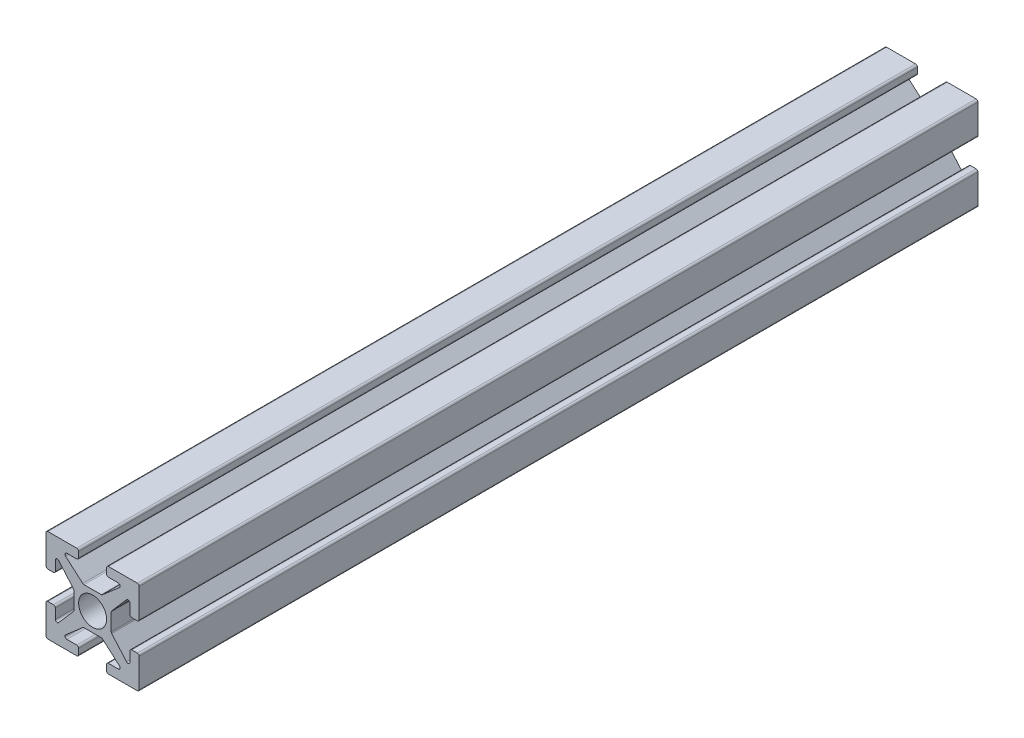
SolidWorks part; units mm, degrees
ref_plane "Front Plane" through (0, 0, 0) normal (0, 0, 1) x (1, 0, 0)
ref_plane "Top Plane" through (0, 0, 0) normal (0, 1, 0) x (1, 0, 0)
ref_plane "Right Plane" through (0, 0, 0) normal (1, 0, 0) x (0, 0, -1)
ref_plane "Plane1" through (0, 5, 0) normal (0, 1, 0) x (1, 0, 0)
sketch "Sketch1" plane through (0, 5, 0) normal (0, 1, 0) x (1, 0, 0)
  line L0 (5, 45) -> (-5, 45)
  line L1 (-5, 45) -> (-5, -45)
  line L2 (-5, -45) -> (5, -45)
  line L3 (5, -45) -> (5, 45)
  point P4 (0, 0)
  point P5 (-5, 0)
  dimension "D1" = 90
  dimension "D2" = 10
extrude "Boss-Extrude1" add sketch "Sketch1" against normal blind 10
sketch "Sketch2" plane through (0, 0, 45) normal (0, 0, 1) x (1, 0, 0)
  line L0 (5, 1.5) -> (4, 1.5)
  line L1 (4, 1.5) -> (4, 2.7593)
  line L2 (3.6493, 2.8908) -> (2, 1)
  line L3 (2, 1) -> (2, -1)
  line L4 (2, -1) -> (3.6493, -2.8908)
  line L5 (4, -2.7593) -> (4, -1.5)
  line L6 (4, -1.5) -> (5, -1.5)
  line L7 (5, -1.5) -> (5, 1.5)
  arc A0 (4, 2.7593) -> (3.6493, 2.8908) centre (3.8, 2.7593) ccw
  arc A1 (3.6493, -2.8908) -> (4, -2.7593) centre (3.8, -2.7593) ccw
extrude "Cut-Extrude1" cut sketch "Sketch2" against normal through all
sketch "Sketch3" plane through (0, 0, 45) normal (0, 0, 1) x (1, 0, 0)
  line L0 (1.5, -5) -> (1.5, -4)
  line L1 (1.5, -4) -> (2.7593, -4)
  line L2 (2.8908, -3.6493) -> (1, -2)
  line L3 (1, -2) -> (-1, -2)
  line L4 (-1, -2) -> (-2.8908, -3.6493)
  line L5 (-2.7593, -4) -> (-1.5, -4)
  line L6 (-1.5, -4) -> (-1.5, -5)
  line L7 (-1.5, -5) -> (1.5, -5)
  arc A0 (2.7593, -4) -> (2.8908, -3.6493) centre (2.7593, -3.8) ccw
  arc A1 (-2.8908, -3.6493) -> (-2.7593, -4) centre (-2.7593, -3.8) ccw
extrude "Cut-Extrude2" cut sketch "Sketch3" against normal through all
sketch "Sketch4" plane through (0, 0, 45) normal (0, 0, 1) x (1, 0, 0)
  line L0 (-5, -1.5) -> (-4, -1.5)
  line L1 (-4, -1.5) -> (-4, -2.7593)
  line L2 (-3.6493, -2.8908) -> (-2, -1)
  line L3 (-2, -1) -> (-2, 1)
  line L4 (-2, 1) -> (-3.6493, 2.8908)
  line L5 (-4, 2.7593) -> (-4, 1.5)
  line L6 (-4, 1.5) -> (-5, 1.5)
  line L7 (-5, 1.5) -> (-5, -1.5)
  arc A0 (-4, -2.7593) -> (-3.6493, -2.8908) centre (-3.8, -2.7593) ccw
  arc A1 (-3.6493, 2.8908) -> (-4, 2.7593) centre (-3.8, 2.7593) ccw
extrude "Cut-Extrude3" cut sketch "Sketch4" against normal through all
sketch "Sketch5" plane through (0, 0, 45) normal (0, 0, 1) x (1, 0, 0)
  line L0 (-1.5, 5) -> (-1.5, 4)
  line L1 (-1.5, 4) -> (-2.7593, 4)
  line L2 (-2.8908, 3.6493) -> (-1, 2)
  line L3 (-1, 2) -> (1, 2)
  line L4 (1, 2) -> (2.8908, 3.6493)
  line L5 (2.7593, 4) -> (1.5, 4)
  line L6 (1.5, 4) -> (1.5, 5)
  line L7 (1.5, 5) -> (-1.5, 5)
  arc A0 (-2.7593, 4) -> (-2.8908, 3.6493) centre (-2.7593, 3.8) ccw
  arc A1 (2.8908, 3.6493) -> (2.7593, 4) centre (2.7593, 3.8) ccw
extrude "Cut-Extrude4" cut sketch "Sketch5" against normal through all
sketch "Sketch6" plane through (0, 0, 0) normal (0, 1, 0) x (1, 0, 0)
  line L0 (1.5, 37) -> (1.25, 36.8498)
  line L1 (0, 45) -> (0, -45)
  line L2 (0, -45) -> (1.5, -45)
  line L3 (1.5, -45) -> (1.5, -37)
  line L4 (1.5, -37) -> (1.25, -36.8498)
  line L5 (1.25, -36.8498) -> (1.25, 36.8498)
  line L6 (1.5, 45) -> (1.5, 37)
  line L7 (0, 45) -> (1.5, 45)
  line L8 (0, 45) -> (0, -45) construction
  line L9 (-1, -45) -> (1, -45) construction
  line L10 (0, 0) -> (7.2534, 0) construction
  point P6 (1.25, 0)
  dimension "D1" = 1.25
  dimension "D2" = 1.5
  dimension "D3" = 121
  dimension "D4" = 8
revolve "Cut-Revolve1" cut sketch "Sketch6" angle 360 about L8 reverse direction yes
fillet "Fillet1" radius 0.2 28 edges at (-5, 1.5, 0) (1.5, -5, 0) (-5, -5, 0) (-1.5, 4, 0) (2, 1, 0) (-4, 1.5, 0) (-2, -1, 0) (-4, -1.5, 0) (-1, -2, 0) (-1.5, -4, 0) (5, -1.5, 0) (1.5, -4, 0) (-5, 5, 0) (4, -1.5, 0) (-2, 1, 0) (4, 1.5, 0) (-5, -1.5, 0) (5, 1.5, 0) (-1.5, -5, 0) (5, 5, 0) (1, -2, 0) (1.5, 5, 0) (5, -5, 0) (1, 2, 0) (2, -1, 0) (-1, 2, 0) (1.5, 4, 0) (-1.5, 5, 0) tangent propagation no
equation "\"length\"=90"
equation "\"D1@Sketch1\"=\"length\""
